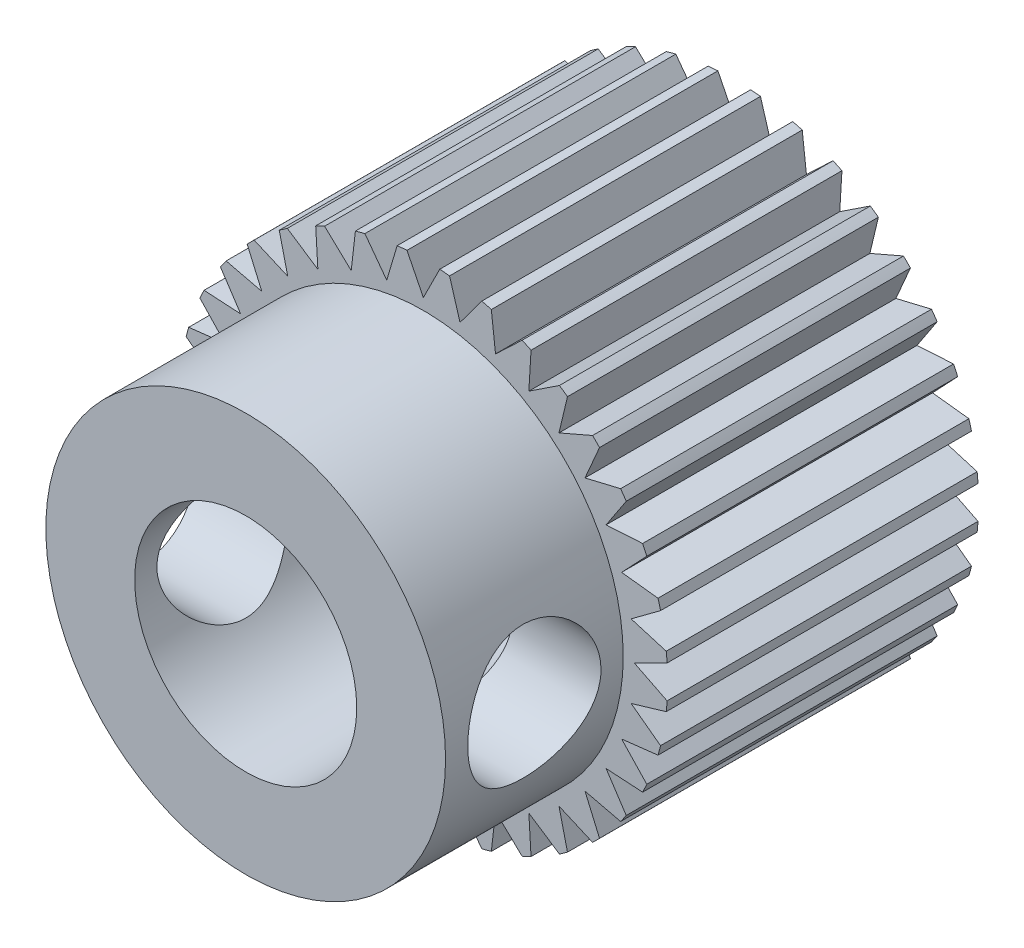
SolidWorks part; units mm, degrees
ref_plane "Front Plane" through (0, 0, 0) normal (0, 0, 1) x (1, 0, 0)
ref_plane "Top Plane" through (0, 0, 0) normal (0, 1, 0) x (1, 0, 0)
ref_plane "Right Plane" through (0, 0, 0) normal (1, 0, 0) x (0, 0, -1)
sketch "Sketch1" plane through (0, 0, 0) normal (0, 0, 1) x (1, 0, 0)
  circle A0 centre (0, 0) radius 5.5
  dimension "D1" = 11
extrude "Boss-Extrude1" add sketch "Sketch1" along normal blind 7
sketch "Sketch2" plane through (0, 0, 7) normal (0, 0, 1) x (1, 0, 0)
  line L0 (0, 0) -> (0, 7.3125) construction
  line L1 (0, 4.75) -> (-0.5, 5.75)
  line L2 (-0.5, 5.75) -> (0.5, 5.75)
  line L3 (0.5, 5.75) -> (0, 4.75)
  line L4 (0.8248, 4.6778) -> (0.5061, 5.7495)
  line L5 (0.5061, 5.7495) -> (1.4909, 5.5758)
  line L6 (1.4909, 5.5758) -> (0.8248, 4.6778)
  line L7 (1.6246, 4.4635) -> (1.4968, 5.5742)
  line L8 (1.4968, 5.5742) -> (2.4365, 5.2322)
  line L9 (2.4365, 5.2322) -> (1.6246, 4.4635)
  line L10 (2.375, 4.1136) -> (2.442, 5.2296)
  line L11 (2.442, 5.2296) -> (3.308, 4.7296)
  line L12 (3.308, 4.7296) -> (2.375, 4.1136)
  line L13 (3.0532, 3.6387) -> (3.313, 4.7261)
  line L14 (3.313, 4.7261) -> (4.0791, 4.0834)
  line L15 (4.0791, 4.0834) -> (3.0532, 3.6387)
  line L16 (3.6387, 3.0532) -> (4.0834, 4.0791)
  line L17 (4.0834, 4.0791) -> (4.7261, 3.313)
  line L18 (4.7261, 3.313) -> (3.6387, 3.0532)
  line L19 (4.1136, 2.375) -> (4.7296, 3.308)
  line L20 (4.7296, 3.308) -> (5.2296, 2.442)
  line L21 (5.2296, 2.442) -> (4.1136, 2.375)
  line L22 (4.4635, 1.6246) -> (5.2322, 2.4365)
  line L23 (5.2322, 2.4365) -> (5.5742, 1.4968)
  line L24 (5.5742, 1.4968) -> (4.4635, 1.6246)
  line L25 (4.6778, 0.8248) -> (5.5758, 1.4909)
  line L26 (5.5758, 1.4909) -> (5.7495, 0.5061)
  line L27 (5.7495, 0.5061) -> (4.6778, 0.8248)
  line L28 (4.75, 0) -> (5.75, 0.5)
  line L29 (5.75, 0.5) -> (5.75, -0.5)
  line L30 (5.75, -0.5) -> (4.75, 0)
  line L31 (4.6778, -0.8248) -> (5.7495, -0.5061)
  line L32 (5.7495, -0.5061) -> (5.5758, -1.4909)
  line L33 (5.5758, -1.4909) -> (4.6778, -0.8248)
  line L34 (4.4635, -1.6246) -> (5.5742, -1.4968)
  line L35 (5.5742, -1.4968) -> (5.2322, -2.4365)
  line L36 (5.2322, -2.4365) -> (4.4635, -1.6246)
  line L37 (4.1136, -2.375) -> (5.2296, -2.442)
  line L38 (5.2296, -2.442) -> (4.7296, -3.308)
  line L39 (4.7296, -3.308) -> (4.1136, -2.375)
  line L40 (3.6387, -3.0532) -> (4.7261, -3.313)
  line L41 (4.7261, -3.313) -> (4.0834, -4.0791)
  line L42 (4.0834, -4.0791) -> (3.6387, -3.0532)
  line L43 (3.0532, -3.6387) -> (4.0791, -4.0834)
  line L44 (4.0791, -4.0834) -> (3.313, -4.7261)
  line L45 (3.313, -4.7261) -> (3.0532, -3.6387)
  line L46 (2.375, -4.1136) -> (3.308, -4.7296)
  line L47 (3.308, -4.7296) -> (2.442, -5.2296)
  line L48 (2.442, -5.2296) -> (2.375, -4.1136)
  line L49 (1.6246, -4.4635) -> (2.4365, -5.2322)
  line L50 (2.4365, -5.2322) -> (1.4968, -5.5742)
  line L51 (1.4968, -5.5742) -> (1.6246, -4.4635)
  line L52 (0.8248, -4.6778) -> (1.4909, -5.5758)
  line L53 (1.4909, -5.5758) -> (0.5061, -5.7495)
  line L54 (0.5061, -5.7495) -> (0.8248, -4.6778)
  line L55 (0, -4.75) -> (0.5, -5.75)
  line L56 (0.5, -5.75) -> (-0.5, -5.75)
  line L57 (-0.5, -5.75) -> (0, -4.75)
  line L58 (-0.8248, -4.6778) -> (-0.5061, -5.7495)
  line L59 (-0.5061, -5.7495) -> (-1.4909, -5.5758)
  line L60 (-1.4909, -5.5758) -> (-0.8248, -4.6778)
  line L61 (-1.6246, -4.4635) -> (-1.4968, -5.5742)
  line L62 (-1.4968, -5.5742) -> (-2.4365, -5.2322)
  line L63 (-2.4365, -5.2322) -> (-1.6246, -4.4635)
  line L64 (-2.375, -4.1136) -> (-2.442, -5.2296)
  line L65 (-2.442, -5.2296) -> (-3.308, -4.7296)
  line L66 (-3.308, -4.7296) -> (-2.375, -4.1136)
  line L67 (-3.0532, -3.6387) -> (-3.313, -4.7261)
  line L68 (-3.313, -4.7261) -> (-4.0791, -4.0834)
  line L69 (-4.0791, -4.0834) -> (-3.0532, -3.6387)
  line L70 (-3.6387, -3.0532) -> (-4.0834, -4.0791)
  line L71 (-4.0834, -4.0791) -> (-4.7261, -3.313)
  line L72 (-4.7261, -3.313) -> (-3.6387, -3.0532)
  line L73 (-4.1136, -2.375) -> (-4.7296, -3.308)
  line L74 (-4.7296, -3.308) -> (-5.2296, -2.442)
  line L75 (-5.2296, -2.442) -> (-4.1136, -2.375)
  line L76 (-4.4635, -1.6246) -> (-5.2322, -2.4365)
  line L77 (-5.2322, -2.4365) -> (-5.5742, -1.4968)
  line L78 (-5.5742, -1.4968) -> (-4.4635, -1.6246)
  line L79 (-4.6778, -0.8248) -> (-5.5758, -1.4909)
  line L80 (-5.5758, -1.4909) -> (-5.7495, -0.5061)
  line L81 (-5.7495, -0.5061) -> (-4.6778, -0.8248)
  line L82 (-4.75, 0) -> (-5.75, -0.5)
  line L83 (-5.75, -0.5) -> (-5.75, 0.5)
  line L84 (-5.75, 0.5) -> (-4.75, 0)
  line L85 (-4.6778, 0.8248) -> (-5.7495, 0.5061)
  line L86 (-5.7495, 0.5061) -> (-5.5758, 1.4909)
  line L87 (-5.5758, 1.4909) -> (-4.6778, 0.8248)
  line L88 (-4.4635, 1.6246) -> (-5.5742, 1.4968)
  line L89 (-5.5742, 1.4968) -> (-5.2322, 2.4365)
  line L90 (-5.2322, 2.4365) -> (-4.4635, 1.6246)
  line L91 (-4.1136, 2.375) -> (-5.2296, 2.442)
  line L92 (-5.2296, 2.442) -> (-4.7296, 3.308)
  line L93 (-4.7296, 3.308) -> (-4.1136, 2.375)
  line L94 (-3.6387, 3.0532) -> (-4.7261, 3.313)
  line L95 (-4.7261, 3.313) -> (-4.0834, 4.0791)
  line L96 (-4.0834, 4.0791) -> (-3.6387, 3.0532)
  line L97 (-3.0532, 3.6387) -> (-4.0791, 4.0834)
  line L98 (-4.0791, 4.0834) -> (-3.313, 4.7261)
  line L99 (-3.313, 4.7261) -> (-3.0532, 3.6387)
  line L100 (-2.375, 4.1136) -> (-3.308, 4.7296)
  line L101 (-3.308, 4.7296) -> (-2.442, 5.2296)
  line L102 (-2.442, 5.2296) -> (-2.375, 4.1136)
  line L103 (-1.6246, 4.4635) -> (-2.4365, 5.2322)
  line L104 (-2.4365, 5.2322) -> (-1.4968, 5.5742)
  line L105 (-1.4968, 5.5742) -> (-1.6246, 4.4635)
  line L106 (-0.8248, 4.6778) -> (-1.4909, 5.5758)
  line L107 (-1.4909, 5.5758) -> (-0.5061, 5.7495)
  line L108 (-0.5061, 5.7495) -> (-0.8248, 4.6778)
  point P114 (0, 0)
  dimension "D1" = 1
  dimension "D2" = 0.5
  dimension "D3" = 1
  dimension "D4" = 4.75
  dimension "D5" = 36
extrude "Cut-Extrude3" cut sketch "Sketch2" against normal blind 7
sketch "Sketch3" plane through (0, 0, 7) normal (0, 0, 1) x (1, 0, 0)
  circle A0 centre (0, 0) radius 4.5
  dimension "D1" = 9
extrude "Boss-Extrude2" add sketch "Sketch3" along normal blind 4
sketch "Sketch4" plane through (0, 0, 0) normal (1, 0, 0) x (0, 0, -1)
  line L0 (-11, 4.5) -> (-11, -4.5) construction
  circle A0 centre (-9, 0) radius 1.5
  dimension "D1" = 3
  dimension "D2" = 2
extrude "Cut-Extrude4" cut sketch "Sketch4" against normal blind 6 and the other way blind 6
sketch "Sketch5" plane through (0, 0, 11) normal (0, 0, 1) x (1, 0, 0)
  circle A0 centre (0, 0) radius 2.5
  dimension "D1" = 5
extrude "Cut-Extrude5" cut sketch "Sketch5" against normal blind 12
